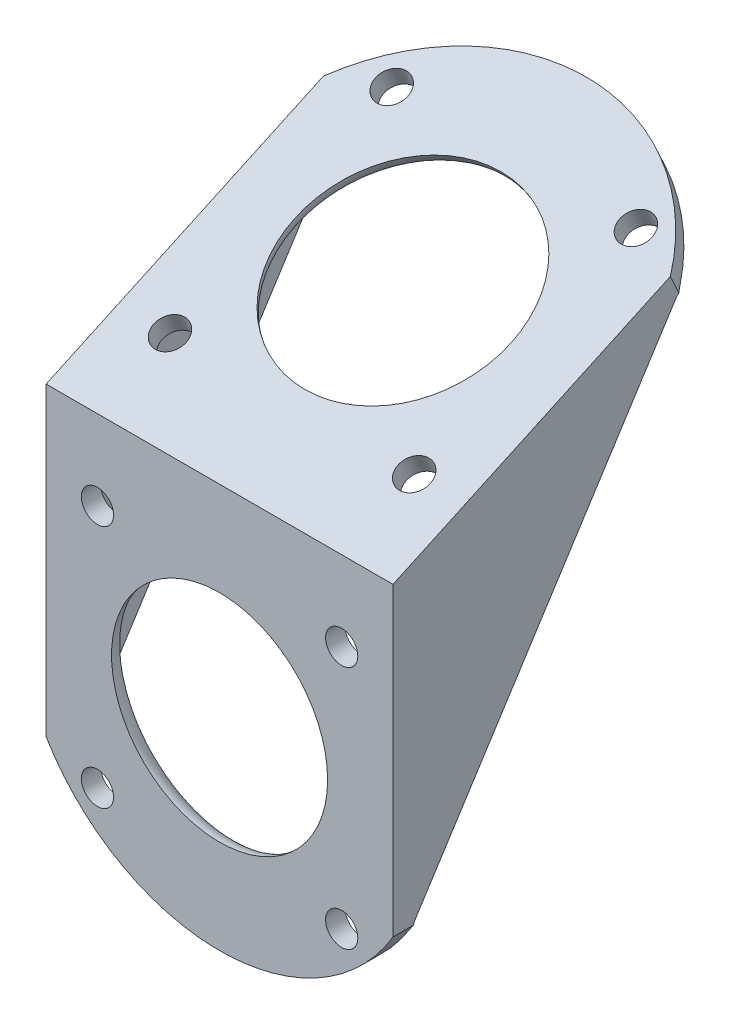
SolidWorks part; units mm, degrees
material "6061-T6 (SS)"
ref_plane "Front Plane" through (0, 0, 0) normal (0, 0, 1) x (1, 0, 0)
ref_plane "Top Plane" through (0, 0, 0) normal (0, 1, 0) x (1, 0, 0)
ref_plane "Right Plane" through (0, 0, 0) normal (1, 0, 0) x (0, 0, -1)
sketch "Sketch1" plane through (0, 0, 0) normal (0, 0, 1) x (1, 0, 0)
  line L0 (-12.5158, 12.5158) -> (-12.5158, -12.5158) construction
  line L1 (-12.5158, -12.5158) -> (12.5158, -12.5158) construction
  line L2 (12.5158, -12.5158) -> (12.5158, 12.5158) construction
  line L3 (12.5158, 12.5158) -> (-12.5158, 12.5158) construction
  line L4 (0, 0) -> (29.0927, 0) construction
  line L5 (0, 0) -> (-27.6955, 0) construction
  line L6 (-27.6955, 10.9507) -> (-27.6955, -10.9507) construction
  line L7 (29.0927, 10.9507) -> (29.0927, -10.9507) construction
  line L10 (-17.78, -10.602) -> (-17.78, 20.701)
  line L11 (-17.78, 20.701) -> (17.78, 20.701)
  line L12 (17.78, -10.602) -> (17.78, 20.701)
  circle A0 centre (0, 0) radius 17.7 construction
  arc A1 (-17.78, -10.602) -> (17.78, -10.602) centre (0, 0) ccw
  circle A2 centre (-12.5158, -12.5158) radius 1.651
  circle A3 centre (12.5158, -12.5158) radius 1.651
  circle A4 centre (12.5158, 12.5158) radius 1.651
  circle A5 centre (-12.5158, 12.5158) radius 1.651
  circle A6 centre (0, 0) radius 11.0731
  dimension "D1" = 41.402
  dimension "D5" = 3.302
  dimension "D6" = 3.302
  dimension "D7" = 3.302
  dimension "D8" = 3.302
  dimension "D9" = 22.1463
  dimension "D2" = 35.56
  dimension "D3" = 17.78
  dimension "D4" = 20.701
extrude "Boss-Extrude1" add sketch "Sketch1" along normal blind 2
ref_plane "Plane1" through (0, 13.7808, -8.8166) normal (0, -0.8424, 0.5389) x (1, 0, 0)
mirror "Mirror1" about plane through (0, 13.7808, -8.8166) normal (0, -0.8424, 0.5389) of "Boss-Extrude1"
sketch "Sketch2" plane through (-17.78, 0, 0) normal (-1, 0, 0) x (0, 0, 1)
  line L0 (0, -10.602) -> (-27.259, 32.0054)
  line L1 (-27.259, 32.0054) -> (0, 19.4215)
  line L2 (0, 19.4215) -> (0, -10.602) construction
  line L3 (0, 19.4215) -> (-27.259, 32.0054) construction
  line L4 (0, 19.4215) -> (0, -10.602)
extrude "Boss-Extrude2" add sketch "Sketch2" against normal blind 2
mirror "Mirror2" about plane through (0, 0, 0) normal (1, 0, 0) of "Boss-Extrude2"
fillet "Fillet2" radius 2 2 edges at (11.0731, 27.5617, -17.6332) (11.0731, 0, 0)
fillet "Fillet3" radius 2 4 edges at (16.78, -10.602, 0) (-16.78, -10.602, 0) (-16.78, 32.0054, -27.259) (16.78, 32.0054, -27.259)
equation "\"D3@Sketch1\"=\"D2@Sketch1\"/2"
equation "\"D4@Sketch1\"=\"D1@Sketch1\"/2"
equation "\"D6@Sketch1\"=\"D5@Sketch1\""
equation "\"D7@Sketch1\"=\"D6@Sketch1\""
equation "\"D8@Sketch1\"=\"D7@Sketch1\""
